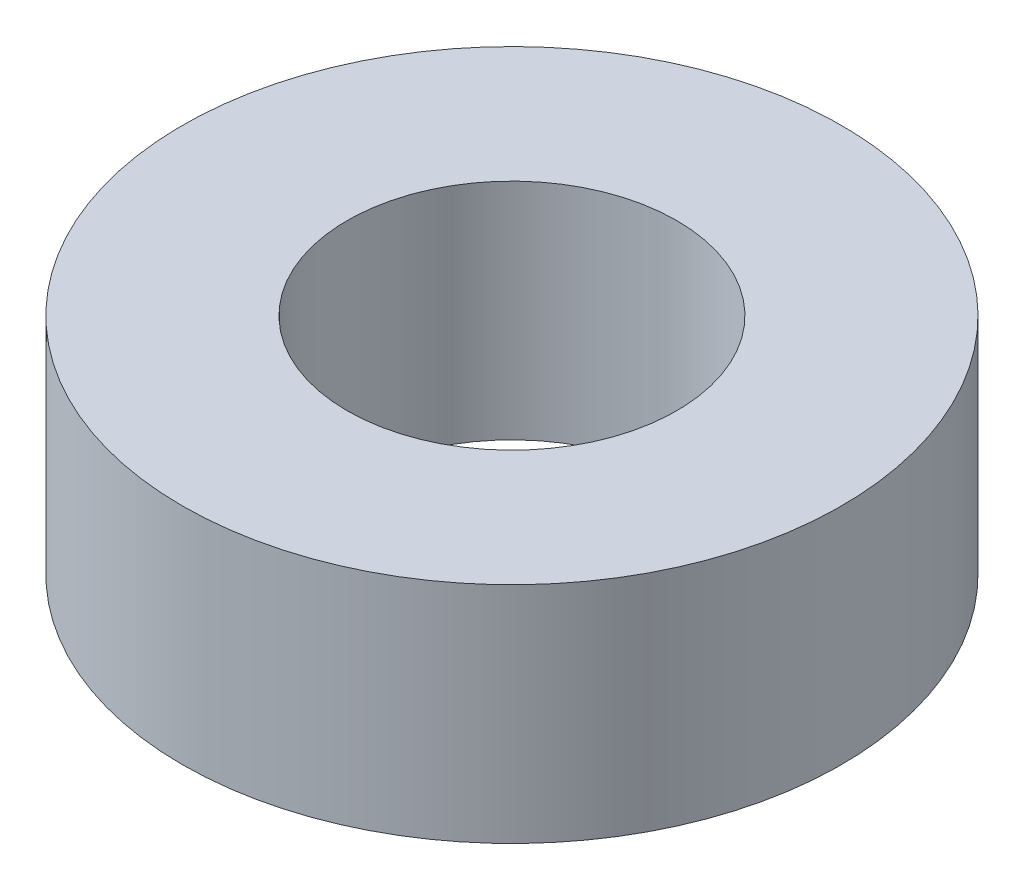
SolidWorks part; units mm, degrees
ref_plane "Front Plane" through (0, 0, 0) normal (0, 0, 1) x (1, 0, 0)
ref_plane "Top Plane" through (0, 0, 0) normal (0, 1, 0) x (1, 0, 0)
ref_plane "Right Plane" through (0, 0, 0) normal (1, 0, 0) x (0, 0, -1)
sketch "Sketch1" plane through (0, 0, 0) normal (0, 1, 0) x (1, 0, 0)
  circle A0 centre (0, 0) radius 25
  dimension "FLANGE_OD" = 50
extrude "Boss-Extrude1" add sketch "Sketch1" along normal blind 17
sketch "Sketch2" plane through (0, 0, 0) normal (0, 1, 0) x (1, 0, 0)
  circle A0 centre (0, 0) radius 12.5
  dimension "BORE_D" = 25
extrude "Cut-Extrude1" cut sketch "Sketch2" along normal through all
sketch "Sketch3" plane through (0, 17, 0) normal (0, 1, 0) x (1, 0, 0)
  circle A0 centre (0, 0) radius 7.6801 construction
  circle A1 centre (-7.6801, 0) radius 1.5498
  dimension "BOLT_D" = 3.0995
  dimension "BOLT_PCD" = 15.3602
extrude "Cut-Extrude2" cut sketch "Sketch3" against normal blind 10.3415 rebuild error yes
pattern_circular "CirPattern1" count 5 over 360 rebuild error yes
